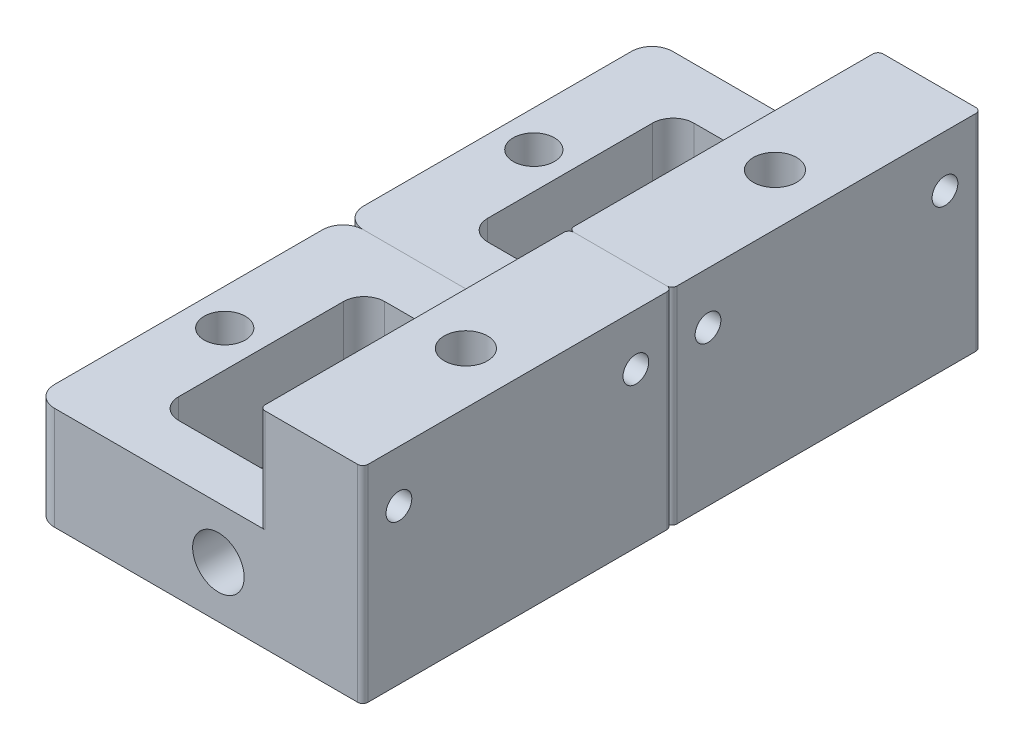
SolidWorks part; units mm, degrees
material "AISI 1045 Steel, cold drawn"
ref_plane "Front Plane" through (0, 0, 0) normal (0, 0, 1) x (1, 0, 0)
ref_plane "Top Plane" through (0, 0, 0) normal (0, 1, 0) x (1, 0, 0)
ref_plane "Right Plane" through (0, 0, 0) normal (1, 0, 0) x (0, 0, -1)
sketch "Sketch1" plane through (0, 0, 0) normal (0, 1, 0) x (1, 0, 0)
  line L1 (7.44, -10) -> (-7.44, -10)
  line L2 (7.44, -10) -> (7.44, 10)
  line L3 (7.44, 10) -> (-7.44, 10)
  line L4 (-7.44, -10) -> (-7.44, 10)
  line L5 (7.44, -10) -> (-7.44, 10) construction
  line L6 (7.44, 10) -> (-7.44, -10) construction
  line L7 (17.44, -15) -> (-14.49, -15)
  line L8 (17.44, -15) -> (17.44, 15)
  line L9 (17.44, 15) -> (-14.49, 15)
  line L10 (-14.49, -15) -> (-14.49, 15)
  line L11 (17.44, -15) -> (-14.49, 15) construction
  line L12 (17.44, 15) -> (-14.49, -15) construction
  point P0 (0, 0)
  point P6 (1.475, 0)
  dimension "D1" = 14.88
  dimension "D2" = 20
  dimension "D3" = 7.05
  dimension "D4" = 5
  dimension "D5" = 10
extrude "Boss-Extrude1" add sketch "Sketch1" along normal blind 10
sketch "Sketch2" plane through (0, 10, 0) normal (0, 1, 0) x (1, 0, 0)
  line L0 (-14.49, -15) -> (17.44, -15) construction
  line L1 (17.44, 15) -> (7.44, 15)
  line L2 (17.44, 15) -> (17.44, -15)
  line L3 (17.44, -15) -> (7.44, -15)
  line L4 (7.44, 15) -> (7.44, -15)
  line L5 (7.44, -10) -> (7.44, 10) construction
extrude "Boss-Extrude2" add sketch "Sketch2" along normal blind 10
hole_wizard "Tap Drill for M5x0.8 Tap1" positions "Sketch3" profile "Sketch4" hole size "M5x0.8" standard "ANSI Metric" end condition through all
sketch "Sketch3" plane through (0, 20, 0) normal (0, 1, 0) x (1, 0, 0)
  line L1 (17.44, 15) -> (7.44, -15) construction
  point P0 (12.44, 0)
sketch "Sketch4" plane through (12.44, 20, 0) normal (1, 0, 0) x (0, 0, 1)
  line L0 (0, 0) -> (0, 20)
  line L1 (0, 20) -> (2.1, 20)
  line L2 (2.1, 20) -> (2.1, 0)
  line L5 (2.1, 0) -> (0, 0)
  line L11 (0, -6.35) -> (0, 107.95) construction
  dimension "Thru Hole Dia." = 4.2
  dimension "Thru Hole Depth" = 20
fillet "Fillet2" radius 2 4 edges at (-7.44, 5, 10) (-7.44, 5, -10) (7.44, 5, -10) (7.44, 5, 10)
sketch "Sketch5" plane through (0, 0, -10) normal (0, 0, 1) x (1, 0, 0)
  line L0 (7.44, 10) -> (7.44, 0) construction
  line L1 (5.44, 10) -> (-5.44, 10) construction
  circle A0 centre (3.42, 5) radius 2.5
  dimension "D2" = 5
  dimension "D1" = 4.02
  dimension "D3" = 5
extrude "Cut-Extrude2" cut sketch "Sketch5" along normal through all
hole_wizard "Tap Drill for M4x0.7 Tap1" positions "Sketch6" profile "Sketch7" hole size "M4x0.7" standard "ANSI Metric" end condition through all
sketch "Sketch6" plane through (0, 0, -10) normal (0, 0, 1) x (1, 0, 0)
  point P0 (3.42, 5)
sketch "Sketch7" plane through (3.42, 5, -10) normal (1, 0, 0) x (0, -1, 0)
  line L0 (0, 0) -> (0, 5)
  line L1 (0, 5) -> (1.65, 5)
  line L2 (1.65, 5) -> (1.65, 0)
  line L5 (1.65, 0) -> (0, 0)
  line L11 (0, -6.35) -> (0, 107.95) construction
  dimension "Thru Hole Dia." = 3.3
  dimension "Thru Hole Depth" = 5
fillet "Fillet3" radius 2 2 edges at (-14.49, 5, -15) (-14.49, 5, 15)
fillet "Fillet4" radius 0.5 4 edges at (17.44, 10, 15) (17.44, 10, -15) (7.44, 15, -15) (7.44, 15, 15)
hole_wizard "Tap Drill for M3x0.5 Tap1" positions "Sketch8" profile "Sketch9" hole size "M3x0.5" standard "ANSI Metric" end condition through all
sketch "Sketch8" plane through (7.44, 0, 0) normal (-1, 0, 0) x (0, 0, 1)
  line L0 (-11.5, 15) -> (11.5, 15) construction
  line L2 (-14.5, 20) -> (14.5, 20) construction
  line L3 (-14.5, 20) -> (-14.5, 10) construction
  point P1 (-11.5, 15)
  point P2 (11.5, 15)
  point P7 (0, 20)
  point P8 (0, 15)
  point P11 (-14.5, 15)
  dimension "D1" = 23
sketch "Sketch9" plane through (7.44, 15, -11.5) normal (0, 1, 0) x (0, 0, 1)
  line L0 (0, 0) -> (0, 10)
  line L1 (0, 10) -> (1.25, 10)
  line L2 (1.25, 10) -> (1.25, 0)
  line L5 (1.25, 0) -> (0, 0)
  line L11 (0, -6.35) -> (0, 107.95) construction
  dimension "Thru Hole Dia." = 2.5
  dimension "Thru Hole Depth" = 10
hole_wizard "Ø4.0 (4) Diameter Hole1" positions "Sketch10" profile "Sketch11" hole size "Ø4.0" standard "ANSI Metric" end condition through all
sketch "Sketch10" plane through (0, 10, 0) normal (0, 1, 0) x (1, 0, 0)
  line L0 (-14.49, 0) -> (-7.44, 0) construction
  line L1 (-14.49, 13) -> (-14.49, -13) construction
  line L2 (-7.44, 8) -> (-7.44, -8) construction
  point P0 (-10.965, 0)
  point P14 (-10.965, 0)
sketch "Sketch11" plane through (-10.965, 10, 0) normal (1, 0, 0) x (0, 0, 1)
  line L0 (0, 0) -> (0, 10)
  line L1 (0, 10) -> (2, 10)
  line L2 (2, 10) -> (2, 0)
  line L5 (2, 0) -> (0, 0)
  line L11 (0, -6.35) -> (0, 107.95) construction
  dimension "Thru Hole Dia." = 4
  dimension "Thru Hole Depth" = 10
mirror "Mirror1" about plane through (17.44, 10, -15) normal (0, 0, 1) of bodies 107
